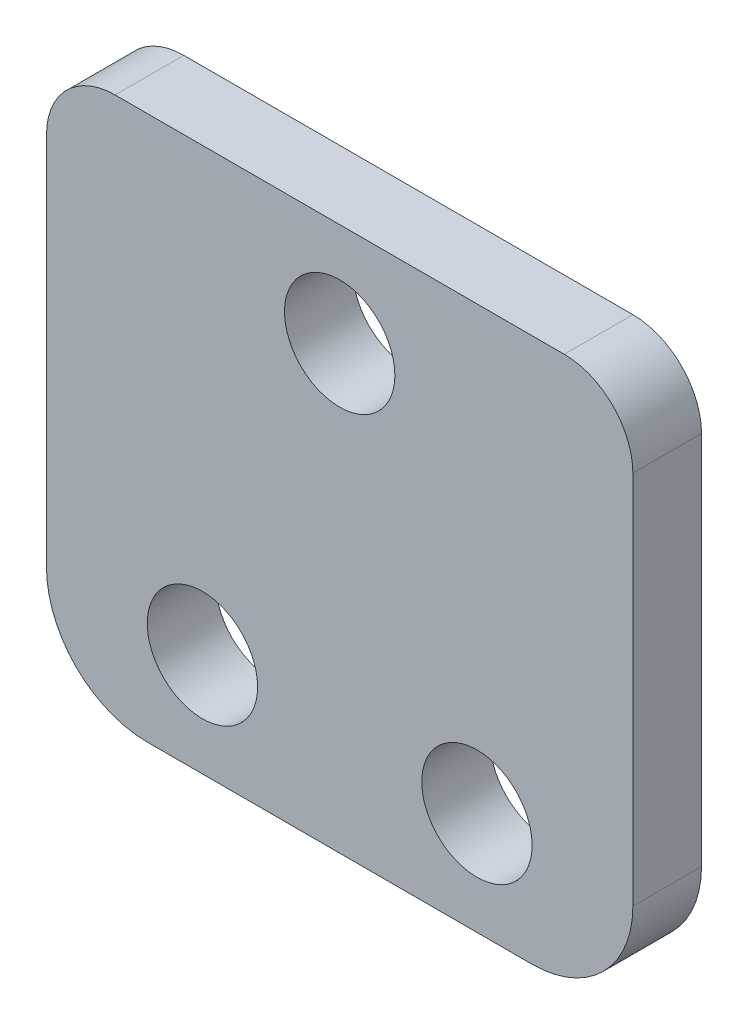
SolidWorks part; units mm, degrees
ref_plane "Front Plane" through (0, 0, 0) normal (0, 0, 1) x (1, 0, 0)
ref_plane "Top Plane" through (0, 0, 0) normal (0, 1, 0) x (1, 0, 0)
ref_plane "Right Plane" through (0, 0, 0) normal (1, 0, 0) x (0, 0, -1)
sketch "Sketch1" plane through (0, 0, 0) normal (0, 0, 1) x (1, 0, 0)
  line L0 (8.9027, 4.6609) -> (-8.9027, 4.6609) construction
  line L1 (8.9027, 4.6609) -> (-8.9027, 4.6609)
  line L3 (10.3886, -4.6609) -> (-10.3886, -4.6609)
  line L4 (8.9027, 4.6609) -> (-8.9027, 4.6609)
  line L5 (-8.9027, -4.6609) -> (8.9027, -4.6609)
  line L6 (8.9027, 4.6609) -> (-8.9027, 4.6609)
  line L7 (-8.9027, -4.6609) -> (8.9027, -4.6609)
  line L8 (13.5636, -1.4859) -> (13.5636, 17.3482)
  line L9 (10.3886, 20.5232) -> (-10.3886, 20.5232)
  line L10 (-13.5636, -1.4859) -> (-13.5636, 17.3482)
  line L11 (-26.467, 20.5232) -> (-70.917, 20.5232) construction
  arc A0 (13.5636, 17.3482) -> (10.3886, 20.5232) centre (10.3886, 17.3482) ccw
  arc A1 (-10.3886, 20.5232) -> (-13.5636, 17.3482) centre (-10.3886, 17.3482) ccw
  arc A2 (8.9027, -4.6609) -> (8.9027, 4.6609) centre (8.9027, 0) ccw
  arc A3 (-8.9027, 4.6609) -> (-8.9027, -4.6609) centre (-8.9027, 0) ccw
  arc A4 (8.9027, -4.6609) -> (8.9027, 4.6609) centre (8.9027, 0) ccw
  arc A5 (-8.9027, 4.6609) -> (-8.9027, -4.6609) centre (-8.9027, 0) ccw
  arc A6 (-10.3886, -4.6609) -> (-13.5636, -1.4859) centre (-10.3886, -1.4859) cw
  arc A7 (10.3886, -4.6609) -> (13.5636, -1.4859) centre (10.3886, -1.4859) ccw
  dimension "D2" = 3.175
  dimension "D1" = 0
extrude "Boss-Extrude1" add sketch "Sketch1" along normal blind 3.175 contours A5 L1 A4 L8 A0 L9 A1 L10 | L1 A5 L3 A4 region at (0, 0, 0) region at (0, 12.3281, 0)
hole_wizard "#10 Clearance Hole1" positions "Sketch2" profile "Sketch3" hole size "#10" standard "ANSI Inch" end condition through all
sketch "Sketch2" plane through (0, 0, 3.175) normal (0, 0, 1) x (1, 0, 0)
  line L0 (0, -4.6609) -> (0, 20.5232) construction
  line L1 (8.9027, -4.6609) -> (-8.9027, -4.6609) construction
  line L2 (10.3886, 20.5232) -> (-10.3886, 20.5232) construction
  line L4 (6.35, 0.1016) -> (-6.35, 0.1016) construction
  point P0 (6.35, 0.1016)
  point P2 (-6.35, 0.1016)
  point P4 (0, 15.7607)
  point P21 (0, 0.1016)
  dimension "D1" = 12.7
  dimension "D2" = 4.7625
  dimension "D3" = 4.7625
sketch "Sketch3" plane through (6.35, 0.1016, 3.175) normal (1, 0, 0) x (0, -1, 0)
  line L0 (0, 0) -> (0, 3.175)
  line L1 (0, 3.175) -> (2.5527, 3.175)
  line L2 (2.5527, 3.175) -> (2.5527, 0)
  line L5 (2.5527, 0) -> (0, 0)
  line L11 (0, -6.35) -> (0, 107.95) construction
  dimension "Thru Hole Dia." = 5.1054
  dimension "Thru Hole Depth" = 3.175
